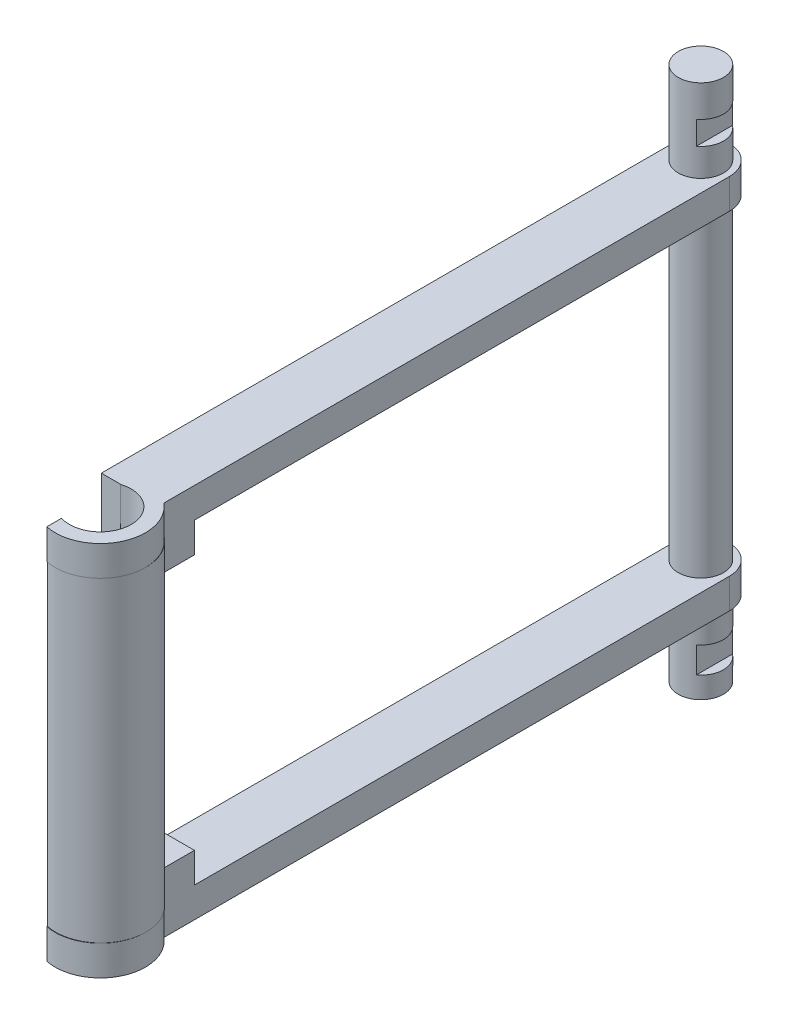
SolidWorks part; units mm, degrees
ref_plane "前视基准面" through (0, 0, 0) normal (0, 0, 1) x (1, 0, 0)
ref_plane "上视基准面" through (0, 0, 0) normal (0, 1, 0) x (1, 0, 0)
ref_plane "右视基准面" through (0, 0, 0) normal (1, 0, 0) x (0, 0, -1)
sketch "草图1" plane through (0, 0, 0) normal (0, 1, 0) x (1, 0, 0)
  line L0 (0, 0) -> (0, -40.0182) construction
  line L5 (1.9, 0) -> (1.9, -40.0182)
  line L6 (-1.9, 0) -> (-1.9, -40.0182)
  arc A0 (1.9, 0) -> (-1.9, 0) centre (0, 0) ccw
  arc A1 (-1.9, -40.0182) -> (1.9, -40.0182) centre (0, -40.0182) ccw
  point P2 (0, -20.0091)
extrude "凸台-拉伸1" add sketch "草图1" along normal blind 2
sketch "草图2" plane through (0, 2, 0) normal (0, 1, 0) x (1, 0, 0)
  circle A0 centre (0, -39.872) radius 3
extrude "凸台-拉伸2" add sketch "草图2" along normal blind 10.5
sketch "草图3" plane through (0, 12.5, 0) normal (0, 1, 0) x (1, 0, 0)
  circle A0 centre (0, -39.9037) radius 2.05
extrude "切除-拉伸1" cut sketch "草图3" against normal blind 12.5
sketch "草图4" plane through (0, 2, 0) normal (0, 1, 0) x (1, 0, 0)
  line L0 (1.9, -37.5504) -> (1.9, 0) construction
  line L1 (-1.9, -37.5504) -> (1.9, -37.5504)
  line L2 (-1.9, -37.5504) -> (-1.9, -35.5504)
  line L3 (-1.9, -35.5504) -> (1.9, -35.5504)
  line L4 (1.9, -37.5504) -> (1.9, -35.5504)
  arc A0 (1.9, -37.5504) -> (0, -36.872) centre (0, -39.872) cw
  arc A1 (1.9, -37.5504) -> (-1.9, -37.5504) centre (0, -39.872) ccw construction
  arc M2 (-1.9, -37.5504) -> (1.9, -37.5504) centre (0, -39.872) cw
  line M3 (1.9, -37.5504) -> (1.9, 0)
  line M5 (-1.9, 0) -> (-1.9, -37.5504)
  dimension "D1" = 2
extrude "凸台-拉伸3" add sketch "草图4" along normal blind 2 contours L3 M5 M2 M3 region at (0, 2, 36.3314)
sketch "草图5" plane through (0, 2, 0) normal (0, -1, 0) x (1, 0, 0)
  circle A0 centre (0, 39.9037) radius 3
  circle A1 centre (0, 39.9037) radius 2.05
extrude "凸台-拉伸4" add sketch "草图5" along normal blind 2
sketch "草图8" plane through (0, 12.5, 0) normal (0, 1, 0) x (1, 0, 0)
  line L1 (-0.6233, -36.9375) -> (-3.5795, -36.9375)
  line L2 (-0.6233, -36.9375) -> (-0.6233, -43.3245)
  line L3 (-0.6233, -43.3245) -> (-3.5795, -43.3245)
  line L4 (-3.5795, -36.9375) -> (-3.5795, -43.3245)
  circle A0 centre (0, -39.872) radius 3 construction
extrude "切除-拉伸3" cut sketch "草图8" against normal blind 12.5
sketch "草图9" plane through (0, 0, 36.9375) normal (0, 0, 1) x (1, 0, 0)
  line L1 (-0.6233, 0) -> (-1.9, 0)
  line L2 (-0.6233, 0) -> (-0.6233, 4)
  line L3 (-0.6233, 4) -> (-1.9, 4)
  line L4 (-1.9, 0) -> (-1.9, 4)
extrude "凸台-拉伸5" add sketch "草图9" along normal blind 1
sketch "草图10" plane through (0, 2, 0) normal (0, 1, 0) x (1, 0, 0)
  circle A1 centre (0, 0) radius 1.5
extrude "凸台-拉伸6" add sketch "草图10" along normal blind 10.5 contours A1
mirror "镜向10" about plane through (0, 12.5, 0) normal (0, 1, 0) of "凸台-拉伸2", "切除-拉伸1", "凸台-拉伸3", "凸台-拉伸4", "切除-拉伸3", "凸台-拉伸5"
mirror "镜向11" about plane through (0, 12.5, 0) normal (0, 1, 0) of "凸台-拉伸1", "镜向10"
sketch "草图11" plane through (0, 12.5, 0) normal (0, 1, 0) x (1, 0, 0)
  circle A0 centre (0, 0) radius 1.5
extrude "凸台-拉伸7" add sketch "草图11" along normal blind 18
sketch "草图12" plane through (0, 0, 0) normal (0, -1, 0) x (1, 0, 0)
  circle A0 centre (0, 0) radius 1.5
extrude "凸台-拉伸8" add sketch "草图12" along normal blind 5
sketch "草图13" plane through (1.9, 0, 0) normal (1, 0, 0) x (0, 0, -1)
  line L1 (2.8744, -3.5836) -> (-2.3476, -3.5836)
  line L2 (2.8744, -3.5836) -> (2.8744, -1.8529)
  line L3 (2.8744, -1.8529) -> (-2.3476, -1.8529)
  line L4 (-2.3476, -3.5836) -> (-2.3476, -1.8529)
  line L5 (2.8744, 26.8395) -> (-2.3476, 26.8395)
  line L6 (2.8744, 26.8395) -> (2.8744, 28.3929)
  line L7 (2.8744, 28.3929) -> (-2.3476, 28.3929)
  line L8 (-2.3476, 26.8395) -> (-2.3476, 28.3929)
extrude "切除-拉伸4" cut sketch "草图13" against normal blind 1
